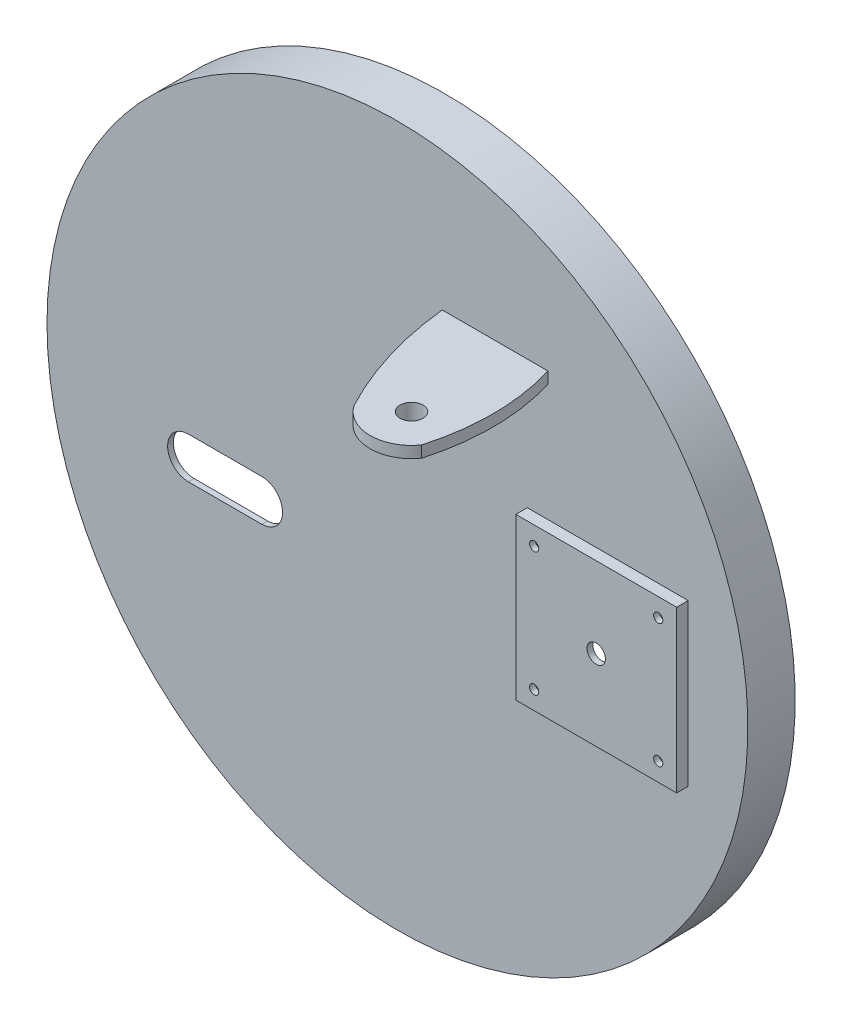
SolidWorks part; units mm, degrees
ref_plane "前视基准面" through (0, 0, 0) normal (0, 0, 1) x (1, 0, 0)
ref_plane "上视基准面" through (0, 0, 0) normal (0, 1, 0) x (1, 0, 0)
ref_plane "右视基准面" through (0, 0, 0) normal (1, 0, 0) x (0, 0, -1)
sketch "草图1" plane through (0, 0, 0) normal (0, 0, 1) x (1, 0, 0)
  circle A0 centre (0, 0) radius 305
  dimension "D1" = 610
extrude "凸台-拉伸1" add sketch "草图1" along normal blind 41.2
sketch "草图2" plane through (0, 0, 41.2) normal (0, 0, 1) x (1, 0, 0)
  line L1 (113, 70) -> (253, 70)
  line L2 (113, 70) -> (113, -70)
  line L3 (113, -70) -> (253, -70)
  line L4 (253, 70) -> (253, -70)
  line L5 (113, 70) -> (253, -70) construction
  line L6 (113, -70) -> (253, 70) construction
  line L7 (129, 54) -> (237, 54) construction
  line L8 (129, 54) -> (129, -54) construction
  line L9 (129, -54) -> (237, -54) construction
  line L10 (237, 54) -> (237, -54) construction
  line L11 (129, 54) -> (237, -54) construction
  line L12 (129, -54) -> (237, 54) construction
  circle A0 centre (183, 0) radius 8
  circle A1 centre (237, 54) radius 4
  circle A2 centre (237, -54) radius 4
  circle A3 centre (129, -54) radius 4
  circle A4 centre (129, 54) radius 4
  point P0 (183, 0)
  point P5 (183, 0)
  dimension "D6" = 16
  dimension "D7" = 8
  dimension "D8" = 8
  dimension "D9" = 8
  dimension "D10" = 8
  dimension "D1" = 140
  dimension "D2" = 140
  dimension "D3" = 113
  dimension "D4" = 108
  dimension "D5" = 108
extrude "凸台-拉伸2" add sketch "草图2" along normal blind 10 contours L2 L1 L4 L3
shell "抽壳1" thickness 5 removed face at (305, 0, 0)
sketch "草图4" plane through (0, 0, 0) normal (0, 0, 1) x (1, 0, 0)
  line L0 (-182, -40) -> (-118, -40) construction
  line L1 (-182, -22) -> (-118, -22)
  line L2 (-182, -58) -> (-118, -58)
  arc A0 (-182, -22) -> (-182, -58) centre (-182, -40) ccw
  arc A1 (-118, -58) -> (-118, -22) centre (-118, -40) ccw
  point P2 (-150, -40)
  dimension "D1" = 100
  dimension "D4" = 100
  dimension "D2" = 36
  dimension "D3" = 40
extrude "切除-拉伸9" cut sketch "草图4" along normal blind 100
sketch "草图5" plane through (0, 0, 41.2) normal (0, 0, 1) x (1, 0, 0)
  line L1 (39, 182.0194) -> (159, 182.0194)
  line L2 (39, 182.0194) -> (39, 172.0194)
  line L3 (39, 172.0194) -> (159, 172.0194)
  line L4 (159, 182.0194) -> (159, 172.0194)
  line L5 (39, 182.0194) -> (159, 172.0194) construction
  line L6 (39, 172.0194) -> (159, 182.0194) construction
  point P0 (99, 177.0194)
  dimension "D1" = 39
  dimension "D2" = 10
  dimension "D3" = 120
extrude "凸台-拉伸3" add sketch "草图5" along normal blind 150
sketch "草图6" plane through (0, 172.0194, 0) normal (0, -1, 0) x (1, 0, 0)
  line L0 (39, 191.2) -> (39, 41.2) construction
  line L1 (39, 41.2) -> (159, 41.2) construction
  arc A0 (39, 41.2) -> (72.4817, 151.3955) centre (337.446, 10.7047) cw
  arc A1 (72.4817, 151.3955) -> (131.7587, 151.869) centre (102.2834, 131.2) cw
  arc A2 (131.7587, 151.869) -> (131, 41.2) centre (-55.6001, 97.8164) cw
  dimension "D1" = 300
  dimension "D2" = 36
  dimension "D3" = 195
  dimension "D4" = 92
  dimension "D5" = 90
sketch "草图9" plane through (0, 172.0194, 0) normal (0, -1, 0) x (1, 0, 0)
  line L0 (39, 191.2) -> (159, 191.2)
  line L1 (159, 191.2) -> (159, 41.2)
  line L2 (159, 41.2) -> (131, 41.2)
  line L3 (39, 191.2) -> (39, 41.2) construction
  line L4 (39, 191.2) -> (39, 41.2)
  arc A0 (72.4817, 151.3955) -> (123.1059, 160.5729) centre (102.3825, 130.6721) cw
  arc A1 (131, 41.2) -> (131.7587, 151.869) centre (-55.6001, 97.8164) ccw construction
  arc A2 (131.7587, 151.869) -> (72.4817, 151.3955) centre (102.2834, 131.2) ccw construction
  arc A3 (72.4817, 151.3955) -> (39, 41.2) centre (337.446, 10.7047) ccw construction
  arc A4 (131, 41.2) -> (131.7587, 151.869) centre (-55.6001, 97.8164) ccw
  arc A5 (131.7587, 151.869) -> (72.4817, 151.3955) centre (102.2834, 131.2) ccw
  arc A6 (72.4817, 151.3955) -> (39, 41.2) centre (337.446, 10.7047) ccw
  point P4 (0, 0)
  point P12 (0, 0)
  point P14 (0, 0)
  line M8 (39, 41.2) -> (159, 41.2)
  line M9 (159, 41.2) -> (159, 191.2)
  line M10 (159, 191.2) -> (39, 191.2)
  line M11 (39, 191.2) -> (39, 41.2)
extrude "切除-拉伸10" cut sketch "草图9" against normal blind 150 contours A6 A5 A4 M8 M9 M10 M11 region at (99, 172.0194, 189.2791)
sketch "草图10" plane through (0, 172.0194, 0) normal (0, -1, 0) x (1, 0, 0)
  circle A0 centre (102.2834, 131.2) radius 10
  dimension "D1" = 20
extrude "切除-拉伸11" cut sketch "草图10" against normal blind 150
sketch "草图11" plane through (0, 172.0194, 0) normal (0, -1, 0) x (1, 0, 0)
  circle A0 centre (102.2834, 131.2) radius 20
  circle A1 centre (102.2834, 131.2) radius 10 construction
  circle A2 centre (102.2834, 131.2) radius 10
  point P3 (0, 0)
  dimension "D1" = 40
extrude "凸台-拉伸4" add sketch "草图11" along normal blind 10
sketch "草图18" plane through (0, 0, 36.2) normal (0, 0, -1) x (-1, 0, 0)
  circle A0 centre (0, 0) radius 85
  dimension "D1" = 170
extrude "凸台-拉伸7" add sketch "草图18" along normal blind 30
sketch "草图19" plane through (0, 0, 6.2) normal (0, 0, -1) x (-1, 0, 0)
  circle A0 centre (0, 0) radius 75
  dimension "D1" = 150
extrude "切除-拉伸12" cut sketch "草图19" against normal blind 30
sketch "草图21" plane through (0, 0, 51.2) normal (0, 0, 1) x (1, 0, 0)
  line L1 (113, 70) -> (253, 70) construction
  line L2 (113, 70) -> (113, -70) construction
  line L3 (113, -70) -> (253, -70) construction
  line L4 (253, 70) -> (253, -70) construction
  line L5 (129, 54) -> (237, 54) construction
  line L6 (129, 54) -> (129, -54) construction
  line L7 (129, -54) -> (237, -54) construction
  line L8 (237, 54) -> (237, -54) construction
  line L9 (129, 54) -> (237, -54) construction
  line L10 (129, -54) -> (237, 54) construction
  circle A0 centre (237, 54) radius 4
  circle A1 centre (129, 54) radius 4
  circle A2 centre (237, -54) radius 4
  circle A3 centre (129, -54) radius 4
  circle A4 centre (183, 0) radius 8
  point P6 (183, 0)
  dimension "D1" = 8
  dimension "D4" = 8
  dimension "D5" = 8
  dimension "D6" = 8
  dimension "D7" = 16
  dimension "D2" = 108
  dimension "D3" = 108
extrude "切除-拉伸13" cut sketch "草图21" against normal blind 30
